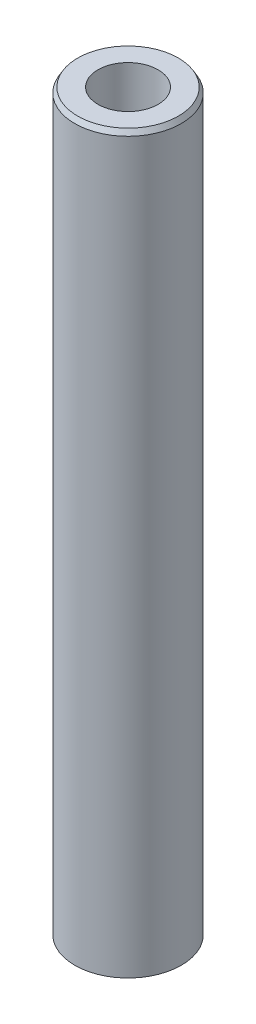
SolidWorks part; units mm, degrees
ref_plane "Front Plane" through (0, 0, 0) normal (0, 0, 1) x (1, 0, 0)
ref_plane "Top Plane" through (0, 0, 0) normal (0, 1, 0) x (1, 0, 0)
ref_plane "Right Plane" through (0, 0, 0) normal (1, 0, 0) x (0, 0, -1)
sketch "Sketch1" plane through (0, 0, 0) normal (0, 1, 0) x (1, 0, 0)
  circle A0 centre (0, 0) radius 25
  dimension "SHAFT_OD" = 50
extrude "Boss-Extrude1" add sketch "Sketch1" along normal blind 346.0402
sketch "Sketch2" plane through (0, 0, 0) normal (0, 1, 0) x (1, 0, 0)
  circle A0 centre (0, 0) radius 14.1102
  dimension "BORE_D" = 28.2205
extrude "Cut-Extrude1" cut sketch "Sketch2" along normal through all
chamfer "Chamfer1" distance 2.3555 angle 30 2 edges at (0, 346.0402, 25) (0, 0, 25) first distance on face at (0, 346.0402, 25) first distance on face at (0, 0, 14.1102)
